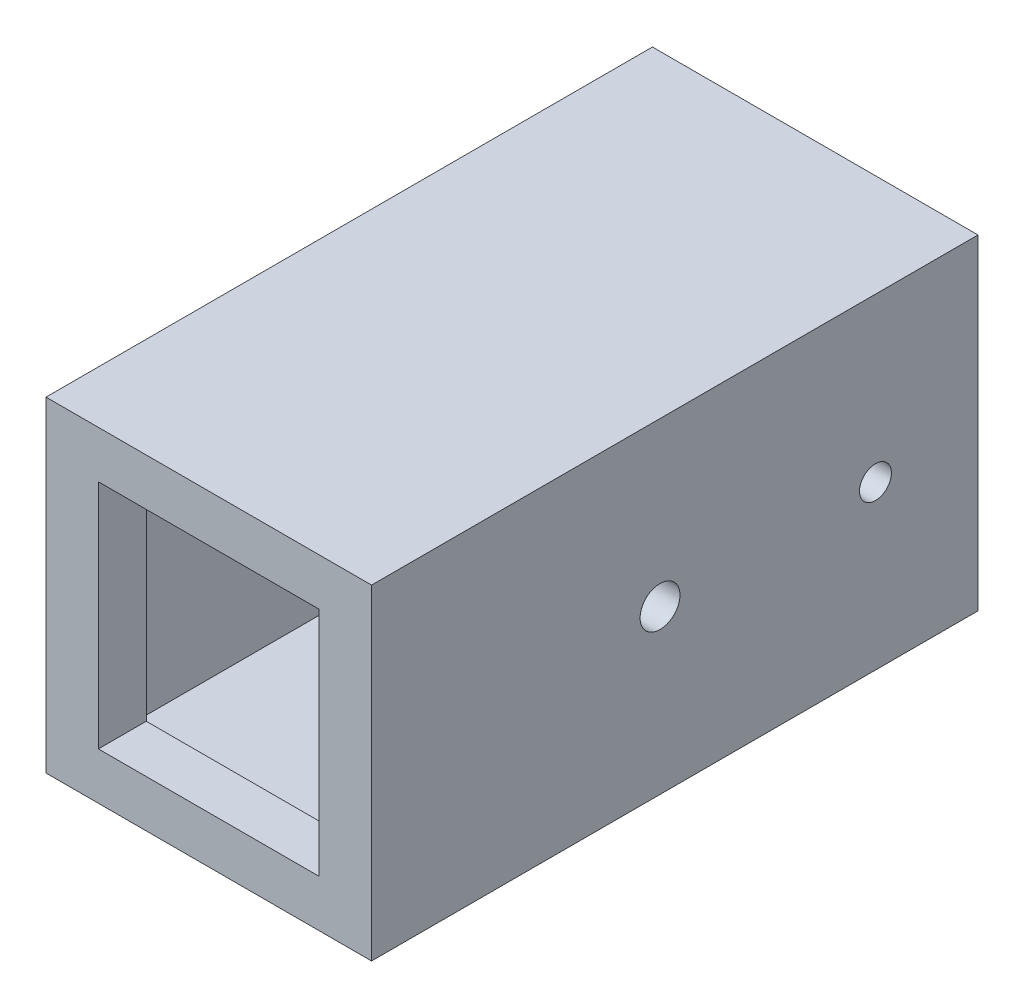
SolidWorks part; units mm, degrees
ref_plane "Front Plane" through (0, 0, 0) normal (0, 0, 1) x (1, 0, 0)
ref_plane "Top Plane" through (0, 0, 0) normal (0, 1, 0) x (1, 0, 0)
ref_plane "Right Plane" through (0, 0, 0) normal (1, 0, 0) x (0, 0, -1)
ref_axis "Axis1" through (0, 0, 0.5) along (0, 0, -1)
sketch "Sketch1" plane through (0, 0, 0) normal (0, 0, 1) x (1, 0, 0)
  line L5 (-10.2, -10.2) -> (10.2, -10.2)
  line L14 (-10.2, -10.2) -> (-10.2, 10.2)
  line L15 (-10.2, 10.2) -> (10.2, 10.2)
  line L16 (10.2, -10.2) -> (10.2, 10.2)
  line L17 (-10.2, -10.2) -> (10.2, 10.2) construction
  line L18 (-10.2, 10.2) -> (10.2, -10.2) construction
  line L19 (-8.2, -8.2) -> (8.2, -8.2)
  line L20 (-8.2, -8.2) -> (-8.2, 8.2)
  line L21 (-8.2, 8.2) -> (8.2, 8.2)
  line L22 (8.2, -8.2) -> (8.2, 8.2)
  line L23 (-8.2, -8.2) -> (8.2, 8.2) construction
  line L24 (-8.2, 8.2) -> (8.2, -8.2) construction
  point P0 (0, 0)
  point P6 (0, 0)
  dimension "D1" = 16.4
  dimension "D2" = 2
extrude "Boss-Extrude1" add sketch "Sketch1" against normal blind 35
sketch "Sketch2" plane through (0, 0, 0) normal (0, 0, 1) x (1, 0, 0)
  line L1 (10.2, 10.2) -> (-10.2, 10.2)
  line L2 (10.2, 10.2) -> (10.2, -10.2)
  line L3 (10.2, -10.2) -> (-10.2, -10.2)
  line L4 (-10.2, 10.2) -> (-10.2, -10.2)
  line L9 (6.9174, -7.2486) -> (-6.9174, -7.2486)
  line L10 (6.9174, -7.2486) -> (6.9174, 7.2486)
  line L11 (6.9174, 7.2486) -> (-6.9174, 7.2486)
  line L12 (-6.9174, -7.2486) -> (-6.9174, 7.2486)
  line L13 (6.9174, -7.2486) -> (-6.9174, 7.2486) construction
  line L14 (6.9174, 7.2486) -> (-6.9174, -7.2486) construction
  point P4 (0, 0)
  point P5 (0, 0)
extrude "Boss-Extrude2" add sketch "Sketch2" along normal blind 3
sketch "Sketch3" plane through (10.2, 0, 0) normal (1, 0, 0) x (0, 0, -1)
  circle A0 centre (28.5758, 0) radius 1.4 construction
  circle A2 centre (15.0758, 0) radius 1.6 construction
  circle A15 centre (28.5758, 0) radius 1.4 construction
  circle A16 centre (15.0758, 0) radius 1.6 construction
  circle A17 centre (15.0758, 0) radius 1.25
  circle A18 centre (28.5758, 0) radius 1
  dimension "D1" = 2.5
  dimension "D2" = 2
extrude "Cut-Extrude1" cut sketch "Sketch3" against normal through all
fillet "Fillet1" radius 1 4 edges at (-8.2, 0, -35) (0, -8.2, -35) (8.2, 0, -35) (0, 8.2, -35)
